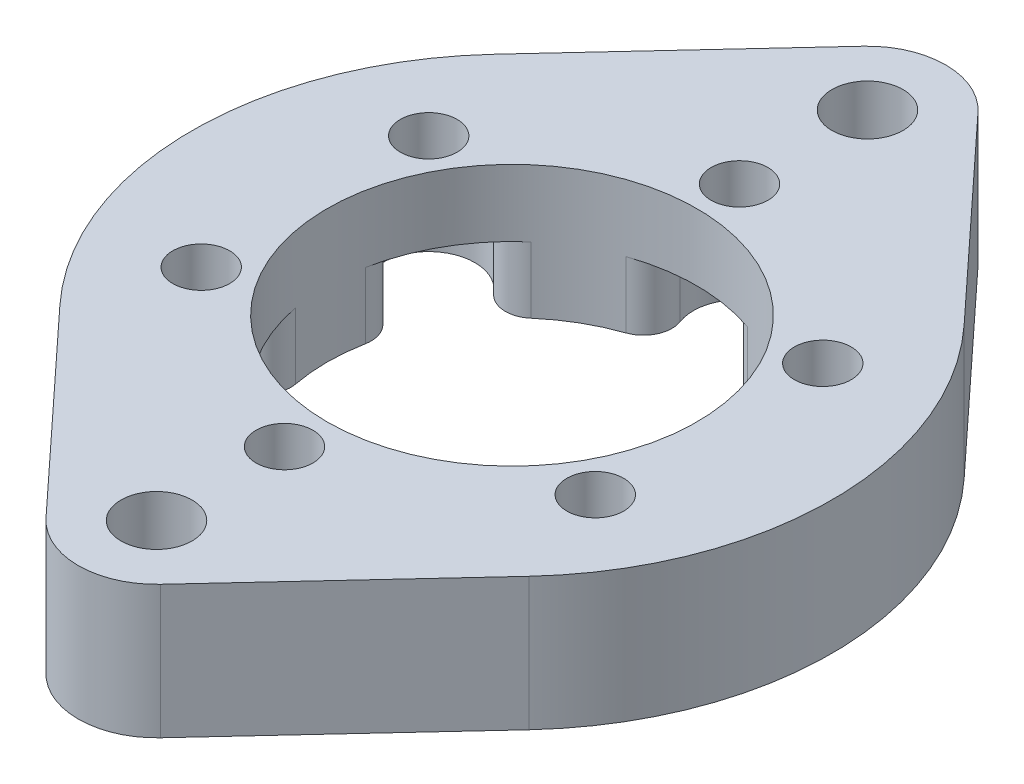
SolidWorks part; units mm, degrees
ref_plane "Front Plane" through (0, 0, 0) normal (0, 0, 1) x (1, 0, 0)
ref_plane "Top Plane" through (0, 0, 0) normal (0, 1, 0) x (1, 0, 0)
ref_plane "Right Plane" through (0, 0, 0) normal (1, 0, 0) x (0, 0, -1)
ref_axis "Axis1" through (0, -54.0054, 0) along (0, 1, 0)
sketch "Sketch1" plane through (0, 0, 0) normal (0, 1, 0) x (1, 0, 0)
  line L0 (0, 13) -> (0, 19) construction
  line L1 (-4.0327, 28.74) -> (-16.4973, 15.3)
  line L3 (-13, 0) -> (13, 0) construction
  line L5 (-4.0327, -28.74) -> (-16.4973, -15.3)
  line L8 (4.0327, 28.74) -> (16.4973, 15.3)
  line L9 (4.0327, -28.74) -> (16.4973, -15.3)
  circle A0 centre (0, 0) radius 13
  circle A1 centre (0, 0) radius 19 construction
  circle A2 centre (0, 16) radius 2
  circle A3 centre (13.8564, 8) radius 2
  circle A4 centre (13.8564, -8) radius 2
  circle A5 centre (0, -16) radius 2
  circle A6 centre (-13.8564, -8) radius 2
  circle A7 centre (-13.8564, 8) radius 2
  circle A8 centre (0, 0) radius 25 construction
  circle A9 centre (0, 25) radius 2.5
  circle A10 centre (0, -25) radius 2.5
  arc A11 (4.0327, 28.74) -> (-4.0327, 28.74) centre (0, 25) ccw
  arc A13 (4.0327, -28.74) -> (-4.0327, -28.74) centre (0, -25) cw
  arc A14 (-16.4973, 15.3) -> (-16.4973, -15.3) centre (0, 0) ccw
  arc A15 (16.4973, -15.3) -> (16.4973, 15.3) centre (0, 0) ccw
  point P21 (0, 0)
  point P27 (0, 0)
  dimension "D1" = 38
  dimension "D2" = 26
  dimension "D3" = 4
  dimension "D5" = 50
  dimension "D6" = 5
  dimension "D8" = 22.5
  dimension "D9" = 3
  dimension "D4" = 6
  dimension "D7" = 2
extrude "Boss-Extrude1" add sketch "Sketch1" along normal blind 9.35
sketch "Sketch2" plane through (0, 9.35, 0) normal (0, 1, 0) x (1, 0, 0)
  circle A0 centre (0, 0) radius 19 construction
  circle A1 centre (0, 0) radius 19
extrude "Cut-Extrude1" [suppressed] cut sketch "Sketch2" against normal blind 3.175
ref_plane "Plane1" through (0, 4.65, 0) normal (0, 1, 0) x (1, 0, 0)
sketch "Sketch3" plane through (0, 0, 0) normal (0, -1, 0) x (1, 0, 0)
  circle A0 centre (0, -16) radius 3.25
  circle A1 centre (-13.8564, -8) radius 3.25
  circle A2 centre (-13.8564, 8) radius 3.25
  circle A3 centre (0, 16) radius 3.25
  circle A4 centre (13.8564, 8) radius 3.25
  circle A5 centre (13.8564, -8) radius 3.25
  point P16 (0, 0)
  dimension "D2" = 6.5
  dimension "D1" = 6
extrude "Cut-Extrude2" cut sketch "Sketch3" against normal up to surface (4.65 mm away) up to plane "Plane1"
fillet "Fillet1" radius 2 12 edges at (1.1257, 2.325, -12.9512) (-1.1257, 2.325, -12.9512) (-10.6532, 2.325, -7.4505) (-11.7789, 2.325, -5.5007) (-11.7789, 2.325, 5.5007) (-10.6532, 2.325, 7.4505) (-1.1257, 2.325, 12.9512) (1.1257, 2.325, 12.9512) (10.6532, 2.325, 7.4505) (11.7789, 2.325, 5.5007) (10.6532, 2.325, -7.4505) (11.7789, 2.325, -5.5007)
